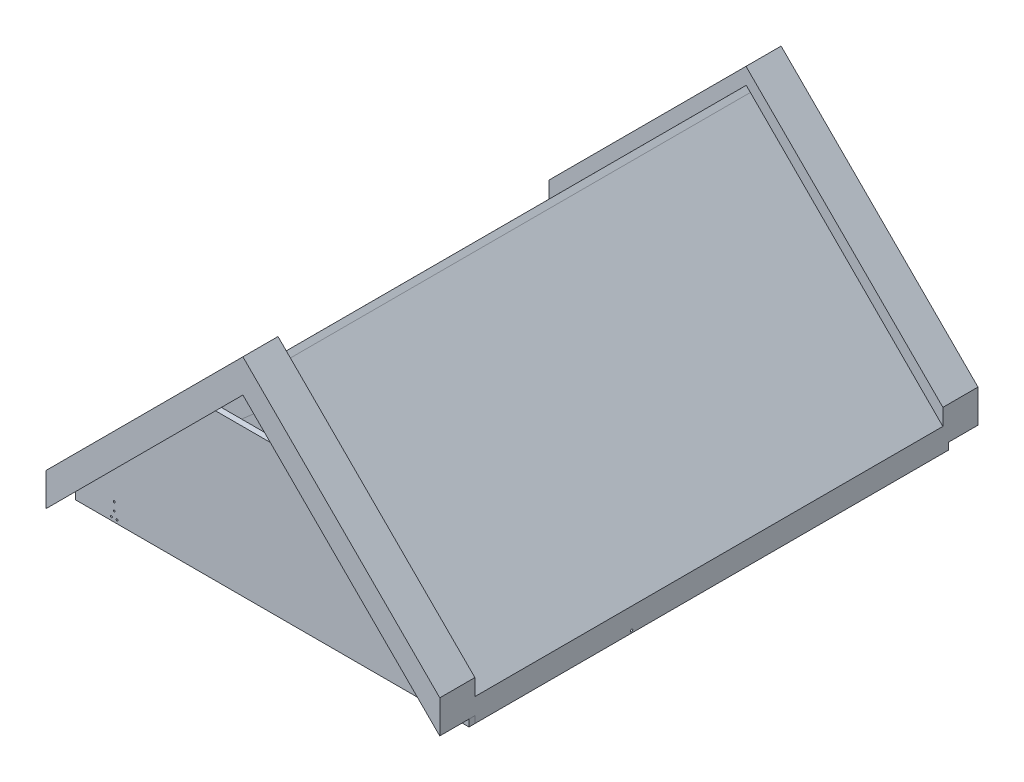
SolidWorks part; units mm, degrees
material "Pine"
ref_plane "Front Plane" through (0, 0, 0) normal (0, 0, 1) x (1, 0, 0)
ref_plane "Top Plane" through (0, 0, 0) normal (0, 1, 0) x (1, 0, 0)
ref_plane "Right Plane" through (0, 0, 0) normal (1, 0, 0) x (0, 0, -1)
sketch "Sketch1" plane through (0, 0, 0) normal (0, 0, 1) x (1, 0, 0)
  line L0 (0, 0) -> (1400, 0)
  line L1 (700, 0) -> (700, 700)
  line L2 (700, 700) -> (0, 0)
  line L3 (700, 700) -> (1400, 0)
  dimension "D1" = 1400
  dimension "D2" = 700
extrude "Boss-Extrude1" add sketch "Sketch1" along normal blind 2000 contours L3 L0 L2
shell "Shell1" thickness 10 removed face at (700, 0, 1000)
sketch "Sketch2" plane through (0, 0, 0) normal (0, -1, 0) x (1, 0, 0)
  line L0 (0, 2000) -> (1400, 2000) construction
  line L1 (-150, 2150) -> (1550, 2150)
  line L2 (-150, 2150) -> (-150, -150)
  line L3 (-150, -150) -> (1550, -150)
  line L4 (1550, 2150) -> (1550, -150)
  line L5 (0, 2000) -> (0, 0) construction
  dimension "D1" = 1700
  dimension "D2" = 2300
  dimension "D3" = 150
  dimension "D4" = 150
sketch "Sketch3" plane through (0, 0, 0) normal (-0.7071, 0.7071, 0) x (0, 0, 1)
  line L10 (2150, 1096.0155) -> (2000, 1096.0155)
  line L11 (2150, 1096.0155) -> (2150, 0)
  line L12 (2150, 0) -> (2000, 0)
  line L13 (2000, 1096.0155) -> (2000, 0)
extrude "Boss-Extrude2" add sketch "Sketch3" along normal blind 100 separate body contours L11 L10 L13 L12
sketch "Sketch7" plane through (700, 700, 0) normal (0.7071, 0.7071, 0) x (0, 0, -1)
  line L5 (-2150, 100) -> (-2000, 100)
  line L6 (-2150, 100) -> (-2150, -989.9495)
  line L7 (-2150, -989.9495) -> (-2000, -989.9495)
  line L8 (-2000, 100) -> (-2000, -989.9495)
extrude "Boss-Extrude4" add sketch "Sketch7" along normal blind 100
sketch "Sketch8" plane through (775, 775, 0) normal (0.7071, 0.7071, 0) x (0, 0, -1)
  line L1 (-2000, 100) -> (-2150, 100)
  line L2 (-2000, 100) -> (-2000, 0)
  line L3 (-2000, 0) -> (-2150, 0)
  line L4 (-2150, 100) -> (-2150, 0)
extrude "Cut-Extrude1" cut sketch "Sketch8" against normal up to vertex (6.066 mm away) and the other way blind 6 up to point (770.7107, 770.7107, 2150)
sketch "Sketch9" plane through (0, 0, 0) normal (-0.7071, -0.7071, 0) x (0, 0, 1)
  line L2 (2000, 100) -> (2150, 100)
  line L3 (2000, 100) -> (2000, 0)
  line L4 (2000, 0) -> (2150, 0)
  line L5 (2150, 100) -> (2150, 0)
extrude "Boss-Extrude5" add sketch "Sketch9" along normal blind 239.05
sketch "Sketch10" plane through (700, -700, 0) normal (0.7071, -0.7071, 0) x (0, 0, -1)
  line L1 (-2000, 989.9495) -> (-2150, 989.9495)
  line L2 (-2000, 989.9495) -> (-2000, 1089.9495)
  line L3 (-2000, 1089.9495) -> (-2150, 1089.9495)
  line L4 (-2150, 989.9495) -> (-2150, 1089.9495)
extrude "Boss-Extrude6" add sketch "Sketch10" along normal blind 399.5
sketch "Sketch13" plane through (0, 0, 2150) normal (0, 0, 1) x (1, 0, 0)
  line L0 (-141.4214, 0) -> (-141.4214, -141.4214)
  line L1 (-150, 0) -> (1550, 0) construction
  line L2 (700, 841.4214) -> (-239.7446, -98.3232) construction
  line L3 (700, 700) -> (-169.0339, -169.0339) construction
  line L4 (-141.4214, -141.4214) -> (-169.0339, -169.0339)
  line L5 (-169.0339, -169.0339) -> (-239.7446, -98.3232)
  line L6 (-239.7446, -98.3232) -> (-141.4214, 0)
  line L7 (1541.4214, 0) -> (1753.1998, -211.7785)
  line L8 (700, 841.4214) -> (1753.1998, -211.7785) construction
  line L9 (1753.1998, -211.7785) -> (1682.4892, -282.4892)
  line L10 (1682.4892, -282.4892) -> (1541.2446, -141.2446)
  line L12 (1541.4214, 0) -> (1541.2446, -141.2446)
extrude "Cut-Extrude4" cut sketch "Sketch13" against normal blind 1197.5
ref_plane "Plane1" through (0, 0, 1000) normal (0, 0, 1) x (1, 0, 0)
mirror "Mirror4" about plane through (0, 0, 1000) normal (0, 0, 1) of bodies 114 108
sketch "Sketch14" plane through (-141.4214, 0, 0) normal (-1, 0, 0) x (0, 0, 1)
  line L0 (0, -141.4214) -> (0, 0) construction
  line L5 (0, -70.7107) -> (2000, -70.7107)
  line L6 (0, -70.7107) -> (0, -170.7107)
  line L7 (0, -170.7107) -> (2000, -170.7107)
  line L8 (2000, -70.7107) -> (2000, -170.7107)
  dimension "D1" = 100
  dimension "D2" = 70.7107
  dimension "D3" = 2000
extrude "Boss-Extrude7" add sketch "Sketch14" against normal blind 25
sketch "Sketch15" plane through (1541.4189, -1.9292, 0) normal (1, -0.0013, 0) x (0, 0, -1)
  line L0 (-2000, 1.9292) -> (-2000, -139.3155) construction
  line L2 (-2000, -68.6932) -> (-2000, -70.8563)
  line L4 (0, -68.6932) -> (0, -70.8563)
  line L6 (-2000, -68.6932) -> (0, -68.6932)
  line L7 (-2000, -68.6932) -> (-2000, -168.6932)
  line L8 (-2000, -168.6932) -> (0, -168.6932)
  line L9 (0, -68.6932) -> (0, -168.6932)
  dimension "D1" = 100
extrude "Boss-Extrude8" add sketch "Sketch15" against normal blind 25 contours L7 L6 L9 L8
ref_plane "Plane2" through (-106.066, -106.066, 0) normal (0.7071, 0.7071, 0) x (0, 0, -1)
sketch "Sketch16" plane through (-106.066, -106.066, 0) normal (0.7071, 0.7071, 0) x (0, 0, -1)
  line L0 (0, -1089.9495) -> (0, 100) construction
  line L1 (-2000, 50) -> (0, 50)
  line L2 (-2000, 50) -> (-2000, 25)
  line L3 (-2000, 25) -> (0, 25)
  line L4 (0, 50) -> (0, 25)
  line L5 (-2000, 50) -> (0, 50) construction
  dimension "D1" = 25
  dimension "D2" = 2000
extrude "Boss-Extrude9" add sketch "Sketch16" along normal blind 1436
ref_plane "Plane3" through (804.0484, -806.0636, 0) normal (-0.7062, 0.708, 0) x (0.708, 0.7062, 0)
sketch "Sketch17" plane through (804.0484, -806.0636, 0) normal (-0.7062, 0.708, 0) x (0.708, 0.7062, 0)
  line L0 (1091.3128, 0) -> (1089.9174, 0) construction
  line L1 (1041.3752, 0) -> (1016.3752, 0)
  line L2 (1041.3752, 0) -> (1041.3752, -2000)
  line L3 (1041.3752, -2000) -> (1016.3752, -2000)
  line L4 (1016.3752, 0) -> (1016.3752, -2000)
  dimension "D1" = 25
  dimension "D2" = 2000
extrude "Boss-Extrude10" add sketch "Sketch17" along normal blind 1436
sketch "Sketch25" plane through (-35.3553, 35.3553, 0) normal (-0.7071, 0.7071, 0) x (0, 0, 1)
  line L6 (0, 1041.4386) -> (2000, 1041.4386)
  line L7 (2000, 1041.4386) -> (2000, 1089.9495)
  line L8 (2000, 1089.9495) -> (2000, 1286)
  line L9 (2000, 1286) -> (0, 1286)
  line L10 (0, 1286) -> (0, 1089.9495)
  line L11 (0, 1089.9495) -> (0, 1041.4386)
  line L12 (0, 1041.4386) -> (2000, 1041.4386)
  line L13 (2000, 1041.4386) -> (2000, 1089.9495)
  line L14 (2000, 1089.9495) -> (2000, 1286)
  line L15 (2000, 1286) -> (0, 1286)
  line L16 (0, 1286) -> (0, 1089.9495)
  line L17 (0, 1089.9495) -> (0, 1041.4386)
  dimension "D1" = 0
sketch "Sketch26" plane through (737.2845, 735.4413, 0) normal (0.708, 0.7062, 0) x (0, 0, -1)
  line L6 (-2000, 101.3034) -> (-2000, 51.3034)
  line L7 (-2000, 51.3034) -> (0, 51.3034)
  line L8 (0, 51.3034) -> (0, 101.3034)
  line L9 (0, 101.3034) -> (0, 297.478)
  line L10 (0, 297.478) -> (-2000, 297.478)
  line L11 (-2000, 297.478) -> (-2000, 101.3034)
  line L12 (-2000, 101.3034) -> (-2000, 51.3034)
  line L14 (0, 51.3034) -> (0, 101.3034)
  line L15 (0, 101.3034) -> (0, 297.478)
  line L16 (0, 297.478) -> (-2000, 297.478)
  line L17 (-2000, 297.478) -> (-2000, 101.3034)
  line L18 (-2000, 51.3034) -> (0, 51.3034)
  dimension "D1" = 0
sketch "Sketch27" plane through (719.5847, 717.7858, 0) normal (-0.708, -0.7062, 0) x (0, 0, 1)
  line L6 (0, 101.2721) -> (0, 51.2721)
  line L7 (0, 51.2721) -> (2000, 51.2721)
  line L8 (2000, 51.2721) -> (2000, 101.2721)
  line L9 (2000, 101.2721) -> (2000, 297.478)
  line L10 (2000, 297.478) -> (0, 297.478)
  line L11 (0, 297.478) -> (0, 101.2721)
  line L12 (0, 101.2721) -> (0, 51.2721)
  line L13 (0, 51.2721) -> (2000, 51.2721)
  line L14 (2000, 51.2721) -> (2000, 101.2721)
  line L15 (2000, 101.2721) -> (2000, 297.478)
  line L16 (2000, 297.478) -> (0, 297.478)
  line L17 (0, 297.478) -> (0, 101.2721)
  dimension "D1" = 0
extrude "Cut-Extrude11" cut sketch "Sketch27" against normal blind 1286
sketch "Sketch28" plane through (-17.6777, 17.6777, 0) normal (0.7071, -0.7071, 0) x (0, 0, -1)
  line L6 (-2000, 1041.4073) -> (0, 1041.4073)
  line L7 (0, 1041.4073) -> (0, 1089.9495)
  line L8 (0, 1089.9495) -> (0, 1286)
  line L9 (0, 1286) -> (-2000, 1286)
  line L10 (-2000, 1286) -> (-2000, 1089.9495)
  line L11 (-2000, 1089.9495) -> (-2000, 1041.4073)
  line L12 (-2000, 1041.4073) -> (0, 1041.4073)
  line L13 (0, 1041.4073) -> (0, 1089.9495)
  line L14 (0, 1089.9495) -> (0, 1286)
  line L15 (0, 1286) -> (-2000, 1286)
  line L16 (-2000, 1286) -> (-2000, 1089.9495)
  line L17 (-2000, 1089.9495) -> (-2000, 1041.4073)
  dimension "D1" = 0
extrude "Cut-Extrude12" cut sketch "Sketch28" against normal blind 1286
sketch "Sketch29" plane through (0, 0, 2000) normal (0, 0, -1) x (-1, 0, 0)
  line L1 (-701.0308, 594.9648) -> (-1466.5902, -170.5946)
  line L2 (-630.3202, 665.6755) -> (116.4214, -81.066)
  line L4 (-701.0308, 594.9648) -> (64.6409, -170.7069)
  line L5 (116.4214, -170.7107) -> (64.6409, -170.7069)
  line L6 (116.4214, -81.066) -> (-701.0308, 736.3862)
  line L7 (-701.0308, 736.3862) -> (-1516.32, -80.9463)
  line L8 (-1516.32, -80.9463) -> (-1516.2758, -116.2758)
  line L9 (-1516.2758, -116.2758) -> (-700, 700)
  line L10 (-700, 700) -> (116.4214, -116.4214)
  line L11 (116.4214, -116.4214) -> (116.4214, -81.066)
  line L12 (-630.3202, 665.6755) -> (-701.0308, 736.3862)
  line L13 (-701.0308, 736.3862) -> (-1516.32, -80.9463)
  line L18 (-1466.5902, -170.5946) -> (-1516.2078, -170.5909)
  line L19 (-1516.32, -80.9463) -> (-1516.2078, -170.5909)
  line L20 (116.4214, -81.066) -> (116.4214, -170.7107)
  dimension "D2" = 100
  dimension "D3" = 100
  dimension "D1" = 0
extrude "Boss-Extrude13" add sketch "Sketch29" along normal blind 50
ref_plane "Plane4" through (0, 0, 1359) normal (0, 0, -1) x (-1, 0, 0)
sketch "Sketch30" plane through (0, 0, 1359) normal (0, 0, -1) x (-1, 0, 0)
  line L8 (-701.0308, 736.3862) -> (-1516.32, -80.9463)
  line L9 (-701.0308, 736.3862) -> (-1516.32, -80.9463)
  line L10 (-1516.2078, -170.5909) -> (-1466.5902, -170.5946)
  line L11 (-1466.5902, -170.5946) -> (-701.0308, 594.9648)
  line L12 (-701.0308, 594.9648) -> (64.6409, -170.7069)
  line L13 (64.6409, -170.7069) -> (116.4214, -170.7107)
  line L14 (-1516.32, -80.9463) -> (-1516.2078, -170.5909)
  line L15 (-1516.32, -80.9463) -> (-1516.2078, -170.5909)
  line L18 (-1516.2078, -170.5909) -> (-1466.5902, -170.5946)
  line L19 (-1466.5902, -170.5946) -> (-701.0308, 594.9648)
  line L20 (-701.0308, 594.9648) -> (64.6409, -170.7069)
  line L21 (64.6409, -170.7069) -> (116.4214, -170.7107)
  line L24 (116.4214, -170.7107) -> (116.4214, -81.066)
  line L25 (116.4214, -170.7107) -> (116.4214, -81.066)
  line L26 (116.4214, -81.066) -> (-701.0308, 736.3862)
  line L27 (116.4214, -81.066) -> (-701.0308, 736.3862)
  dimension "D1" = 0
extrude "Boss-Extrude14" add sketch "Sketch30" along normal blind 50
ref_plane "Plane5" through (0, 0, 691) normal (0, 0, -1) x (-1, 0, 0)
sketch "Sketch31" plane through (0, 0, 691) normal (0, 0, -1) x (-1, 0, 0)
  line L8 (116.4214, -81.066) -> (-701.0308, 736.3862)
  line L9 (-701.0308, 736.3862) -> (-1516.32, -80.9463)
  line L10 (-1516.32, -80.9463) -> (-1516.2078, -170.5909)
  line L11 (-1516.2078, -170.5909) -> (-1466.5902, -170.5946)
  line L12 (-1466.5902, -170.5946) -> (-701.0308, 594.9648)
  line L13 (-701.0308, 594.9648) -> (64.6409, -170.7069)
  line L14 (64.6409, -170.7069) -> (116.4214, -170.7107)
  line L15 (116.4214, -170.7107) -> (116.4214, -81.066)
  line L16 (116.4214, -81.066) -> (-701.0308, 736.3862)
  line L17 (-701.0308, 736.3862) -> (-1516.32, -80.9463)
  line L18 (-1516.32, -80.9463) -> (-1516.2078, -170.5909)
  line L19 (-1516.2078, -170.5909) -> (-1466.5902, -170.5946)
  line L20 (-1466.5902, -170.5946) -> (-701.0308, 594.9648)
  line L21 (-701.0308, 594.9648) -> (64.6409, -170.7069)
  line L22 (64.6409, -170.7069) -> (116.4214, -170.7107)
  line L23 (116.4214, -170.7107) -> (116.4214, -81.066)
  dimension "D1" = 0
extrude "Boss-Extrude15" add sketch "Sketch31" along normal blind 50
ref_plane "Plane6" through (0, 0, 50) normal (0, 0, -1) x (-1, 0, 0)
sketch "Sketch33" plane through (0, 0, 50) normal (0, 0, -1) x (-1, 0, 0)
  line L8 (116.4214, -170.7107) -> (116.4214, -81.066)
  line L9 (116.4214, -81.066) -> (-701.0308, 736.3862)
  line L10 (-701.0308, 736.3862) -> (-1516.32, -80.9463)
  line L11 (-1516.32, -80.9463) -> (-1516.2078, -170.5909)
  line L12 (-1516.2078, -170.5909) -> (-1466.5902, -170.5946)
  line L13 (-1466.5902, -170.5946) -> (-701.0308, 594.9648)
  line L14 (-701.0308, 594.9648) -> (64.6409, -170.7069)
  line L15 (64.6409, -170.7069) -> (116.4214, -170.7107)
  line L16 (116.4214, -170.7107) -> (116.4214, -81.066)
  line L17 (116.4214, -81.066) -> (-701.0308, 736.3862)
  line L18 (-701.0308, 736.3862) -> (-1516.32, -80.9463)
  line L19 (-1516.32, -80.9463) -> (-1516.2078, -170.5909)
  line L20 (-1516.2078, -170.5909) -> (-1466.5902, -170.5946)
  line L21 (-1466.5902, -170.5946) -> (-701.0308, 594.9648)
  line L22 (-701.0308, 594.9648) -> (64.6409, -170.7069)
  line L23 (64.6409, -170.7069) -> (116.4214, -170.7107)
  dimension "D1" = 0
extrude "Boss-Extrude16" add sketch "Sketch33" along normal blind 50
sketch "Sketch35" plane through (0, 0, 2000) normal (0, 0, 1) x (1, 0, 0)
  line L0 (60.3572, -45.7088) -> (1341.7044, -45.7088)
  line L1 (701.0308, 594.9648) -> (-64.6409, -170.7069) construction
  line L2 (-39.6428, -145.7088) -> (1441.7044, -145.7088)
  line L3 (1466.5902, -170.5946) -> (701.0308, 594.9648) construction
  line L4 (60.3572, -45.7088) -> (-39.6428, -145.7088)
  line L5 (1341.7044, -45.7088) -> (1441.7044, -145.7088)
  line L9 (-64.6409, -170.7069) -> (-116.4214, -170.7107) construction
  line L10 (-64.6409, -170.7069) -> (-116.4214, -170.7107)
  point P10 (-90.5311, -170.7088)
  line M8 (-64.6409, -170.7069) -> (701.0308, 594.9648)
  line M9 (701.0308, 594.9648) -> (1466.5902, -170.5946)
  dimension "D1" = 100
  dimension "D2" = 25
extrude "Boss-Extrude17" add sketch "Sketch35" against normal blind 50 separate body contours L2 L0 M8 M9 region at (701.0308, -96.9153, 2000)
sketch "Sketch36" plane through (0, 0, 1359) normal (0, 0, -1) x (-1, 0, 0)
  line L4 (39.6428, -145.7088) -> (-60.3572, -45.7088)
  line L5 (-60.3572, -45.7088) -> (-1341.7044, -45.7088)
  line L6 (-1341.7044, -45.7088) -> (-1441.7044, -145.7088)
  line L7 (-1441.7044, -145.7088) -> (39.6428, -145.7088)
  line L8 (39.6428, -145.7088) -> (-60.3572, -45.7088)
  line L9 (-60.3572, -45.7088) -> (-1341.7044, -45.7088)
  line L10 (-1341.7044, -45.7088) -> (-1441.7044, -145.7088)
  line L11 (-1441.7044, -145.7088) -> (39.6428, -145.7088)
  dimension "D1" = 0
extrude "Boss-Extrude18" add sketch "Sketch36" along normal blind 50 separate body
sketch "Sketch37" plane through (0, 0, 691) normal (0, 0, -1) x (-1, 0, 0)
  line L4 (-1441.7044, -145.7088) -> (39.6428, -145.7088)
  line L5 (39.6428, -145.7088) -> (-60.3572, -45.7088)
  line L6 (-60.3572, -45.7088) -> (-1341.7044, -45.7088)
  line L7 (-1341.7044, -45.7088) -> (-1441.7044, -145.7088)
  line L8 (-1441.7044, -145.7088) -> (39.6428, -145.7088)
  line L9 (39.6428, -145.7088) -> (-60.3572, -45.7088)
  line L10 (-60.3572, -45.7088) -> (-1341.7044, -45.7088)
  line L11 (-1341.7044, -45.7088) -> (-1441.7044, -145.7088)
  dimension "D1" = 0
extrude "Boss-Extrude19" add sketch "Sketch37" along normal blind 50 separate body
sketch "Sketch38" plane through (0, 0, 50) normal (0, 0, -1) x (-1, 0, 0)
  line L4 (-1341.7044, -45.7088) -> (-1441.7044, -145.7088)
  line L5 (-1441.7044, -145.7088) -> (39.6428, -145.7088)
  line L6 (39.6428, -145.7088) -> (-60.3572, -45.7088)
  line L7 (-60.3572, -45.7088) -> (-1341.7044, -45.7088)
  line L8 (-1341.7044, -45.7088) -> (-1441.7044, -145.7088)
  line L9 (-1441.7044, -145.7088) -> (39.6428, -145.7088)
  line L10 (39.6428, -145.7088) -> (-60.3572, -45.7088)
  line L11 (-60.3572, -45.7088) -> (-1341.7044, -45.7088)
  dimension "D1" = 0
extrude "Boss-Extrude20" add sketch "Sketch38" along normal blind 50 separate body
sketch "Sketch34" plane through (0.0125, -170.7021, 0) normal (0.0001, -1, 0) x (1, 0.0001, 0)
  line L0 (1441.6938, 1950) -> (1441.6938, 2000) construction
  line L5 (1.0188, 2000) -> (1401.0188, 2000)
  line L6 (1.0188, 2000) -> (1.0188, 0)
  line L7 (1.0188, 0) -> (1401.0188, 0)
  line L8 (1401.0188, 2000) -> (1401.0188, 0)
  line L9 (-39.6534, 2000) -> (1441.6938, 2000) construction
  dimension "D1" = 1400
  dimension "D2" = 2000
  dimension "D3" = 40.675
extrude "Boss-Extrude21" add sketch "Sketch34" against normal blind 25 separate body
sketch "Sketch39" plane through (0, 0, 2000) normal (0, 0, 1) x (1, 0, 0)
  line L0 (-64.6409, -170.7069) -> (1466.5902, -170.5946)
  line L1 (458.0438, 458.0438) -> (941.9562, 458.0438)
  line L10 (-141.4214, -170.7107) -> (-116.4214, -170.7107)
  line L11 (-116.4214, -170.7107) -> (-64.6409, -170.7069)
  line L12 (-64.6409, -170.7069) -> (701.0308, 594.9648)
  line L13 (701.0308, 594.9648) -> (1466.5902, -170.5946)
  line L14 (1466.5902, -170.5946) -> (1516.2078, -170.5909)
  line L15 (1516.2078, -170.5909) -> (1541.2078, -170.6222)
  line L16 (1541.2078, -170.6222) -> (1541.2446, -141.2446)
  line L17 (1541.2446, -141.2446) -> (700, 700)
  line L18 (700, 700) -> (-141.4214, -141.4214)
  line L19 (-141.4214, -141.4214) -> (-141.4214, -170.7107)
  line L20 (-141.4214, -170.7107) -> (-116.4214, -170.7107)
  line L21 (-116.4214, -170.7107) -> (-64.6409, -170.7069)
  line L24 (1466.5902, -170.5946) -> (1516.2078, -170.5909)
  line L25 (1516.2078, -170.5909) -> (1541.2078, -170.6222)
  line L26 (1541.2078, -170.6222) -> (1541.2446, -141.2446)
  line L27 (1541.2446, -141.2446) -> (941.9562, 458.0438)
  line L28 (458.0438, 458.0438) -> (-141.4214, -141.4214)
  line L29 (-141.4214, -141.4214) -> (-141.4214, -170.7107)
  dimension "D2" = 483.9123
  dimension "D1" = 0
extrude "Boss-Extrude22" add sketch "Sketch39" along normal blind 25 separate body
sketch "Sketch40" plane through (0, 0, 0) normal (0, 0, -1) x (-1, 0, 0)
  line L0 (-1466.5902, -170.5946) -> (64.6409, -170.7069)
  line L2 (-941.9562, 458.0438) -> (-458.0438, 458.0438)
  line L10 (141.4214, -170.7107) -> (141.4214, -141.4214)
  line L11 (141.4214, -141.4214) -> (-700, 700)
  line L12 (-700, 700) -> (-1541.2446, -141.2446)
  line L13 (-1541.2446, -141.2446) -> (-1541.2078, -170.6222)
  line L14 (-1541.2078, -170.6222) -> (-1516.2078, -170.5909)
  line L15 (-1516.2078, -170.5909) -> (-1466.5902, -170.5946)
  line L16 (-1466.5902, -170.5946) -> (-701.0308, 594.9648)
  line L17 (-701.0308, 594.9648) -> (64.6409, -170.7069)
  line L18 (64.6409, -170.7069) -> (116.4214, -170.7107)
  line L19 (116.4214, -170.7107) -> (141.4214, -170.7107)
  line L20 (141.4214, -170.7107) -> (141.4214, -141.4214)
  line L21 (141.4214, -141.4214) -> (-458.0438, 458.0438)
  line L22 (-941.9562, 458.0438) -> (-1541.2446, -141.2446)
  line L23 (-1541.2446, -141.2446) -> (-1541.2078, -170.6222)
  line L24 (-1541.2078, -170.6222) -> (-1516.2078, -170.5909)
  line L25 (-1516.2078, -170.5909) -> (-1466.5902, -170.5946)
  line L28 (64.6409, -170.7069) -> (116.4214, -170.7107)
  line L29 (116.4214, -170.7107) -> (141.4214, -170.7107)
  dimension "D2" = 483.9123
  dimension "D1" = 0
extrude "Boss-Extrude23" add sketch "Sketch40" along normal blind 25
sketch "Sketch41" plane through (0.0125, -170.7021, 0) normal (0.0001, -1, 0) x (1, 0.0001, 0)
  line L0 (12.3035, 1864.4107) -> (16.9035, 1864.4244)
  line L1 (1.0015, 1999.9778) -> (12.3035, 1864.4107)
  line L2 (0.9765, 2008.4278) -> (1.0015, 1999.9778)
  line L3 (9.9764, 2008.4544) -> (0.9765, 2008.4278)
  line L4 (10.0015, 2000.0045) -> (9.9764, 2008.4544)
  line L5 (27.8014, 2000.0573) -> (10.0015, 2000.0045)
  line L6 (27.7764, 2008.5072) -> (27.8014, 2000.0573)
  line L7 (36.7763, 2008.5339) -> (27.7764, 2008.5072)
  line L8 (36.8014, 2000.084) -> (36.7763, 2008.5339)
  line L9 (26.3034, 1864.4523) -> (36.8014, 2000.084)
  line L10 (21.7034, 1864.4386) -> (26.3034, 1864.4523)
  line L77 (1376.4806, 1864.3486) -> (1381.0806, 1864.3622)
  line L78 (1365.1787, 1999.9157) -> (1376.4806, 1864.3486)
  line L79 (1365.1536, 2008.3656) -> (1365.1787, 1999.9157)
  line L80 (1374.1536, 2008.3923) -> (1365.1536, 2008.3656)
  line L81 (1374.1786, 1999.9423) -> (1374.1536, 2008.3923)
  line L82 (1391.9786, 1999.9951) -> (1374.1786, 1999.9423)
  line L83 (1391.9535, 2008.445) -> (1391.9786, 1999.9951)
  line L84 (1400.9535, 2008.4717) -> (1391.9535, 2008.445)
  line L85 (1400.9785, 2000.0218) -> (1400.9535, 2008.4717)
  line L86 (1390.4806, 1864.3901) -> (1400.9785, 2000.0218)
  line L87 (1385.8806, 1864.3764) -> (1390.4806, 1864.3901)
  spline S0 degree 3 poles (27.8669, 1977.9724) (22.8369, 1977.9575) (22.8518, 1972.9275) (27.8818, 1972.9424) (32.9118, 1972.9573) (32.8969, 1977.9873) (27.8669, 1977.9724) (22.8369, 1977.9575) (22.8518, 1972.9275) knots -0.5 0 0 0 0.5 0.5 0.5 1 1 1 1.5 1.5 1.5 weights 1 0.333333 0.333333 1 0.333333 0.333333 1 0.333333 0.333333 only from (27.8669, 1977.9724) to (27.8669, 1977.9724)
  spline S1 degree 3 poles (19.1096, 1929.8312) (14.3096, 1929.817) (14.3238, 1925.017) (19.1238, 1925.0312) (23.9238, 1925.0455) (23.9095, 1929.8454) (19.1096, 1929.8312) (14.3096, 1929.817) (14.3238, 1925.017) knots -0.5 0 0 0 0.5 0.5 0.5 1 1 1 1.5 1.5 1.5 weights 1 0.333333 0.333333 1 0.333333 0.333333 1 0.333333 0.333333 only from (19.1096, 1929.8312) to (19.1096, 1929.8312)
  spline S32 degree 3 poles (19.2519, 1881.8314) (14.4519, 1881.8172) (14.4661, 1877.0172) (19.2661, 1877.0314) (24.0661, 1877.0457) (24.0518, 1881.8457) (19.2519, 1881.8314) (14.4519, 1881.8172) (14.4661, 1877.0172) knots -0.5 0 0 0 0.5 0.5 0.5 1 1 1 1.5 1.5 1.5 weights 1 0.333333 0.333333 1 0.333333 0.333333 1 0.333333 0.333333 only from (19.2519, 1881.8314) to (19.2519, 1881.8314)
  spline S33 degree 3 poles (10.0366, 1988.1686) (4.5086, 1988.1522) (4.525, 1982.6242) (10.053, 1982.6406) (15.581, 1982.657) (15.5646, 1988.185) (10.0366, 1988.1686) (4.5086, 1988.1522) (4.525, 1982.6242) knots -0.5 0 0 0 0.5 0.5 0.5 1 1 1 1.5 1.5 1.5 weights 1 0.333333 0.333333 1 0.333333 0.333333 1 0.333333 0.333333 only from (10.0366, 1988.1686) to (10.0366, 1988.1686)
  spline S34 degree 3 poles (16.9035, 1864.4244) (16.9177, 1859.6244) (21.7177, 1859.6386) (21.7034, 1864.4386) knots 0 0 0 0 1 1 1 1 weights 1 0.333333 0.333333 1
  spline S35 degree 3 poles (1392.044, 1977.9102) (1387.014, 1977.8953) (1387.029, 1972.8653) (1392.0589, 1972.8802) (1397.0889, 1972.8951) (1397.074, 1977.9251) (1392.044, 1977.9102) (1387.014, 1977.8953) (1387.029, 1972.8653) knots -0.5 0 0 0 0.5 0.5 0.5 1 1 1 1.5 1.5 1.5 weights 1 0.333333 0.333333 1 0.333333 0.333333 1 0.333333 0.333333 only from (1392.044, 1977.9102) to (1392.044, 1977.9102)
  spline S36 degree 3 poles (1383.2867, 1929.769) (1378.4867, 1929.7548) (1378.501, 1924.9548) (1383.3009, 1924.969) (1388.1009, 1924.9833) (1388.0867, 1929.7833) (1383.2867, 1929.769) (1378.4867, 1929.7548) (1378.501, 1924.9548) knots -0.5 0 0 0 0.5 0.5 0.5 1 1 1 1.5 1.5 1.5 weights 1 0.333333 0.333333 1 0.333333 0.333333 1 0.333333 0.333333 only from (1383.2867, 1929.769) to (1383.2867, 1929.769)
  spline S37 degree 3 poles (1383.429, 1881.7692) (1378.629, 1881.755) (1378.6433, 1876.955) (1383.4432, 1876.9693) (1388.2432, 1876.9835) (1388.229, 1881.7835) (1383.429, 1881.7692) (1378.629, 1881.755) (1378.6433, 1876.955) knots -0.5 0 0 0 0.5 0.5 0.5 1 1 1 1.5 1.5 1.5 weights 1 0.333333 0.333333 1 0.333333 0.333333 1 0.333333 0.333333 only from (1383.429, 1881.7692) to (1383.429, 1881.7692)
  spline S38 degree 3 poles (1374.2137, 1988.1064) (1368.6857, 1988.09) (1368.7021, 1982.562) (1374.2301, 1982.5784) (1379.7581, 1982.5948) (1379.7417, 1988.1228) (1374.2137, 1988.1064) (1368.6857, 1988.09) (1368.7021, 1982.562) knots -0.5 0 0 0 0.5 0.5 0.5 1 1 1 1.5 1.5 1.5 weights 1 0.333333 0.333333 1 0.333333 0.333333 1 0.333333 0.333333 only from (1374.2137, 1988.1064) to (1374.2137, 1988.1064)
  spline S39 degree 3 poles (1381.0806, 1864.3622) (1381.0948, 1859.5622) (1385.8948, 1859.5764) (1385.8806, 1864.3764) knots 0 0 0 0 1 1 1 1 weights 1 0.333333 0.333333 1
extrude "Cut-Extrude14" [suppressed] cut sketch "Sketch41" against normal blind 10 contours S33 | S0 | S1 | S36 | S35 | S38
ref_plane "Plane7" through (0, 0, 2010) normal (0, 0, 1) x (1, 0, 0)
sketch "Sketch42" plane through (0, 0, 2010) normal (0, 0, 1) x (-1, 0, 0)
  line L88 (-1349.3821, 25.2633) -> (-1353.982, 25.2497)
  line L89 (-1353.982, 25.2497) -> (-1362.944, 132.749)
  line L90 (-1362.944, 132.749) -> (-1363.0523, 169.2734)
  line L91 (-1363.0523, 169.2734) -> (-1356.3091, 169.2934)
  line L92 (-1356.3091, 169.2934) -> (-1356.284, 160.8434)
  line L93 (-1356.284, 160.8434) -> (-1338.5085, 160.8961)
  line L94 (-1338.5085, 160.8961) -> (-1338.5336, 169.3595)
  line L95 (-1331.5821, 133.8178) -> (-1339.9821, 25.2912)
  line L96 (-1339.9821, 25.2912) -> (-1344.5821, 25.2775)
  line L97 (-1331.5821, 133.8178) -> (-1331.7903, 169.3595)
  line L99 (-1331.7903, 169.3595) -> (-1338.5336, 169.3595)
  spline S2 degree 3 poles (-1344.5821, 25.2775) (-1344.5679, 20.4775) (-1349.3678, 20.4633) (-1349.3821, 25.2633) knots 0 0 0 0 1 1 1 1 weights 1 0.333333 0.333333 1
  spline S3 degree 3 poles (-1338.449, 149.0603) (-1332.921, 149.0766) (-1332.9047, 143.5487) (-1338.4326, 143.5323) (-1343.9606, 143.5159) (-1343.977, 149.0439) (-1338.449, 149.0603) (-1332.921, 149.0766) (-1332.9047, 143.5487) knots -0.5 0 0 0 0.5 0.5 0.5 1 1 1 1.5 1.5 1.5 weights 1 0.333333 0.333333 1 0.333333 0.333333 1 0.333333 0.333333 only from (-1338.449, 149.0603) to (-1338.449, 149.0603)
  spline S4 degree 3 poles (-1347.0337, 42.6703) (-1342.2337, 42.6846) (-1342.2194, 37.8846) (-1347.0194, 37.8704) (-1351.8194, 37.8561) (-1351.8336, 42.6561) (-1347.0337, 42.6703) (-1342.2337, 42.6846) (-1342.2194, 37.8846) knots -0.5 0 0 0 0.5 0.5 0.5 1 1 1 1.5 1.5 1.5 weights 1 0.333333 0.333333 1 0.333333 0.333333 1 0.333333 0.333333 only from (-1347.0337, 42.6703) to (-1347.0337, 42.6703)
  spline S5 degree 3 poles (-1347.176, 90.6701) (-1342.376, 90.6844) (-1342.3617, 85.8844) (-1347.1617, 85.8701) (-1351.9617, 85.8559) (-1351.9759, 90.6559) (-1347.176, 90.6701) (-1342.376, 90.6844) (-1342.3617, 85.8844) knots -0.5 0 0 0 0.5 0.5 0.5 1 1 1 1.5 1.5 1.5 weights 1 0.333333 0.333333 1 0.333333 0.333333 1 0.333333 0.333333 only from (-1347.176, 90.6701) to (-1347.176, 90.6701)
  spline S6 degree 3 poles (-1356.2186, 138.7585) (-1351.1886, 138.7734) (-1351.1737, 133.7435) (-1356.2036, 133.7285) (-1361.2336, 133.7136) (-1361.2485, 138.7436) (-1356.2186, 138.7585) (-1351.1886, 138.7734) (-1351.1737, 133.7435) knots -0.5 0 0 0 0.5 0.5 0.5 1 1 1 1.5 1.5 1.5 weights 1 0.333333 0.333333 1 0.333333 0.333333 1 0.333333 0.333333 only from (-1356.2186, 138.7585) to (-1356.2186, 138.7585)
  dimension "D1" = 1331.5821
  dimension "D2" = 1331.7903
  dimension "D3" = 1338.449
  dimension "D4" = 1338.5085
  dimension "D5" = 1338.5336
  dimension "D6" = 1339.9821
  dimension "D7" = 1344.5821
  dimension "D8" = 1347.0337
  dimension "D9" = 1347.176
  dimension "D10" = 1349.3821
  dimension "D11" = 1356.3091
  dimension "D12" = 1356.2186
  dimension "D13" = 1356.284
  dimension "D14" = 1363.0523
  dimension "D15" = 1362.944
  dimension "D16" = 25.2497
  dimension "D17" = 132.749
  dimension "D18" = 149.0603
  dimension "D20" = 42.6703
  dimension "D21" = 90.6701
  dimension "D23" = 133.8178
extrude "Cut-Extrude15" [suppressed] cut sketch "Sketch42" against normal blind 20
sketch "Sketch43" plane through (0, 0, 0) normal (1, 0, 0) x (0, 0, -1)
  line L0 (-2000, -170.6222) -> (25, -170.6222) construction
  line L1 (-2150, 0) -> (-2150, -141.2446) construction
  circle A0 centre (-1330, -160.6222) radius 5
  dimension "D1" = 10
  dimension "D2" = 10
  dimension "D3" = 820
extrude "Cut-Extrude16" cut sketch "Sketch43" against normal through all both and the other way through all
sketch "Sketch45" plane through (0, 0, 2000) normal (0, 0, 1) x (1, 0, 0)
  line L0 (1.0294, -145.7021) -> (1.0313, -170.7021) construction
  line L1 (13.0316, -156.2021) -> (37.0316, -156.2021) construction
  line L2 (5.0316, -175.7021) -> (45.0316, -175.7021) construction
  line L3 (25.0316, -175.7021) -> (25.0316, -156.2021) construction
  line L4 (25.0316, -156.2021) -> (25.0316, -129.2021) construction
  line L5 (25.0316, -129.2021) -> (25.0316, -95.2021) construction
  line L7 (1365.0316, -156.0997) -> (1389.0316, -156.0997) construction
  line L8 (1357.0316, -175.5997) -> (1397.0316, -175.5997) construction
  line L9 (1377.0316, -175.5997) -> (1377.0316, -156.0997) construction
  line L10 (1377.0316, -156.0997) -> (1377.0316, -129.0997) construction
  line L11 (1377.0316, -129.0997) -> (1377.0316, -95.0997) construction
  line L13 (1401.0294, -145.5994) -> (1401.0313, -170.5994) construction
  line L14 (1401.0313, -170.5994) -> (1.0313, -170.7021) construction
  circle A0 centre (13.0316, -156.2021) radius 4
  circle A1 centre (37.0316, -156.2021) radius 4
  circle A2 centre (25.0316, -129.2021) radius 4
  circle A3 centre (25.0316, -95.2021) radius 4
  circle A4 centre (1365.0316, -156.0997) radius 4
  circle A5 centre (1389.0316, -156.0997) radius 4
  circle A6 centre (1377.0316, -129.0997) radius 4
  circle A7 centre (1377.0316, -95.0997) radius 4
  point P11 (25.0316, -156.2021)
  point P24 (1377.0316, -156.0997)
  dimension "D6" = 8
  dimension "D8" = 8
  dimension "D10" = 8
  dimension "D14" = 8
  dimension "D16" = 8
  dimension "D18" = 8
  dimension "D1" = 4
  dimension "D2" = 40
  dimension "D3" = 19.5
  dimension "D4" = 5
  dimension "D5" = 24
  dimension "D7" = 27
  dimension "D9" = 34
  dimension "D11" = 40
  dimension "D12" = 19.5
  dimension "D13" = 24
  dimension "D15" = 27
  dimension "D17" = 34
  dimension "D19" = 4
  dimension "D20" = 5
extrude "Cut-Extrude17" cut sketch "Sketch45" along direction (0, 0, 1) on the side of the normal blind 30
